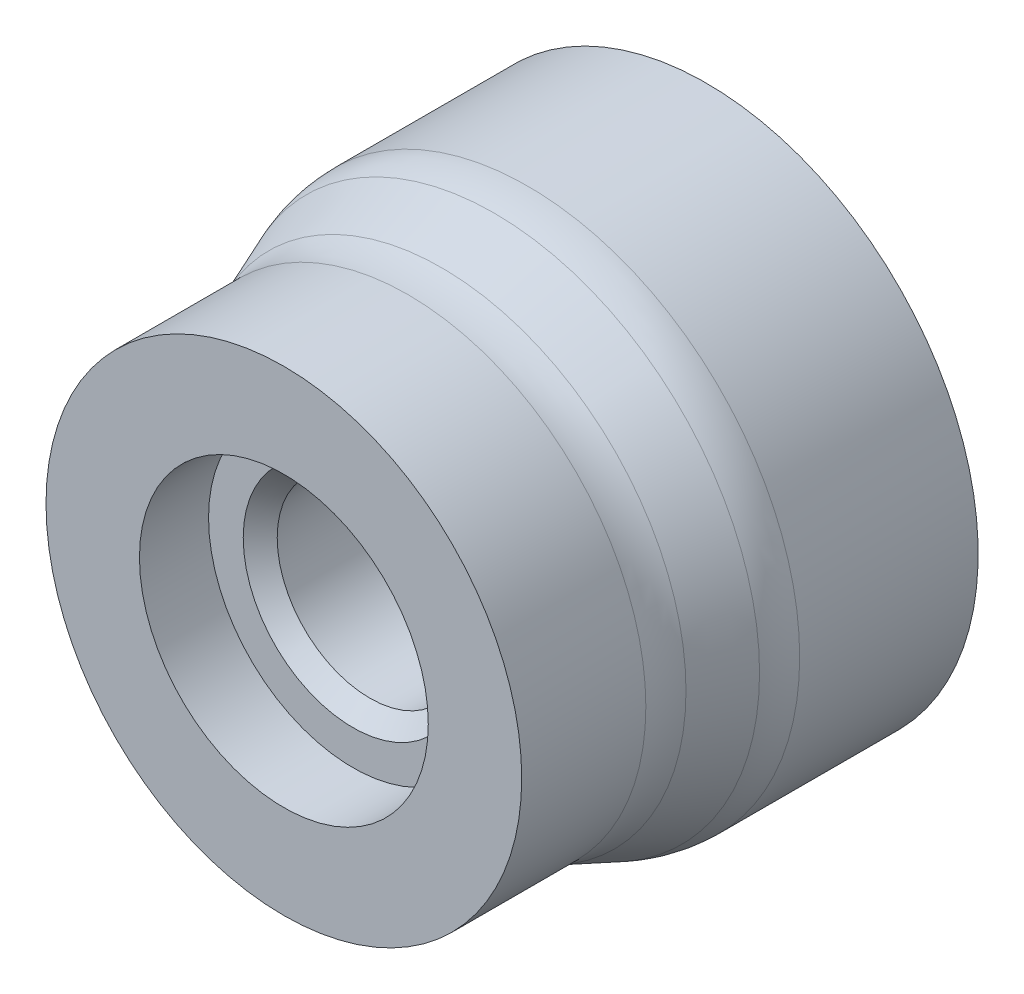
SolidWorks part; units mm, degrees
ref_plane "Front Plane" through (0, 0, 0) normal (0, 0, 1) x (1, 0, 0)
ref_plane "Top Plane" through (0, 0, 0) normal (0, 1, 0) x (1, 0, 0)
ref_plane "Right Plane" through (0, 0, 0) normal (1, 0, 0) x (0, 0, -1)
sketch "Sketch1" plane through (0, 0, 0) normal (0, 0, 1) x (1, 0, 0)
  circle A0 centre (0, 0) radius 21
  circle A1 centre (0, 0) radius 7.9375 construction
  circle A2 centre (0, 0) radius 8.1875
  dimension "D1" = 15.875
  dimension "D3" = 42
  dimension "D2" = 0.25
extrude "Boss-Extrude1" add sketch "Sketch1" along normal blind 37.3
sketch "Sketch2" plane through (0, 0, 0) normal (0, 0, -1) x (-1, 0, 0)
  circle A0 centre (0, 0) radius 24
  circle A1 centre (0, 0) radius 21 construction
  circle A2 centre (0, 0) radius 21
  dimension "D1" = 48
extrude "Boss-Extrude2" add sketch "Sketch2" against normal offset from surface (27.3 mm away) 10 up to face at (21, 0, 37.3)
chamfer "Chamfer1" distance 4 distance2 10 1 edges at (24, 0, 27.3) first distance on face at (24, 0, 27.3)
sketch "Sketch3" plane through (0, 0, 37.3) normal (0, 0, 1) x (1, 0, 0)
  circle A0 centre (0, 0) radius 12.75
  dimension "D1" = 25.5
extrude "Cut-Extrude1" cut sketch "Sketch3" against normal blind 6.1
sketch "Sketch4" plane through (0, 0, 0) normal (0, 0, -1) x (-1, 0, 0)
  circle A0 centre (0, 0) radius 11.5
  dimension "D1" = 23
extrude "Cut-Extrude2" cut sketch "Sketch4" against normal blind 2
chamfer "Chamfer2" distance 1.5 angle 45 2 edges at (8.1875, 0, 31.2) (-8.1875, 0, 2)
fillet "Fillet1" radius 8 2 edges at (24, 0, 17.3) (-21, 0, 24.8)
